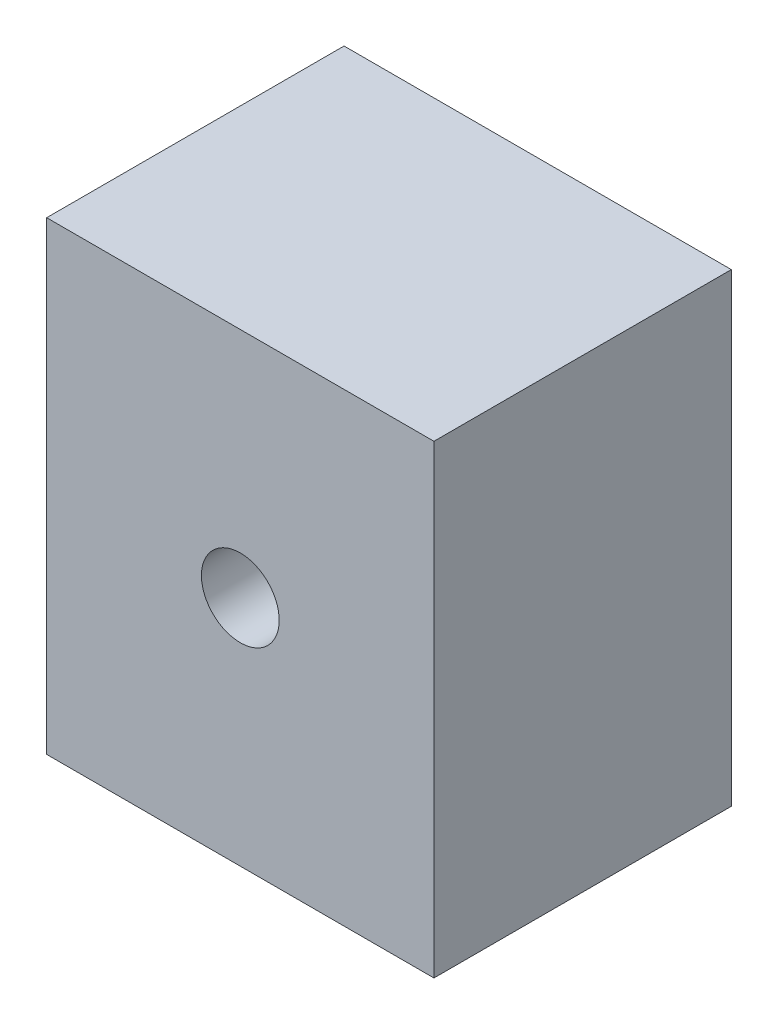
SolidWorks part; units mm, degrees
ref_plane "Front Plane" through (0, 0, 0) normal (0, 0, 1) x (1, 0, 0)
ref_plane "Top Plane" through (0, 0, 0) normal (0, 1, 0) x (1, 0, 0)
ref_plane "Right Plane" through (0, 0, 0) normal (1, 0, 0) x (0, 0, -1)
sketch "Sketch1" plane through (0, 0, 0) normal (0, 1, 0) x (1, 0, 0)
  line L1 (-8.4644, 10) -> (8.4644, 10)
  line L2 (-8.4644, 10) -> (-8.4644, -3)
  line L3 (-8.4644, -3) -> (8.4644, -3)
  line L4 (8.4644, 10) -> (8.4644, -3)
extrude "Boss-Extrude1" add sketch "Sketch1" along normal mid plane 20.32 separate body
sketch "Sketch2" plane through (0, 0, -10) normal (0, 0, -1) x (-1, 0, 0)
  line L1 (2.8001, 0) -> (1.4001, 2.425)
  line L2 (1.4001, 2.425) -> (-1.4001, 2.425)
  line L3 (-1.4001, 2.425) -> (-2.8001, 0)
  line L4 (-2.8001, 0) -> (-1.4001, -2.425)
  line L5 (-1.4001, -2.425) -> (1.4001, -2.425)
  line L6 (1.4001, -2.425) -> (2.8001, 0)
  circle A0 centre (0, 0) radius 2.425 construction
  circle A1 centre (0, 0) radius 1.7
extrude "Cut-Extrude1" cut sketch "Sketch2" against normal blind 9.906 contours L5 L6 L1 L2 L3 L4 A1 region at (-2.036, -1.1755, -10)
extrude "Cut-Extrude2" cut sketch "Sketch2<3>" against normal blind 15.748 contours A1 region at (0, 0, -10)
sketch "Sketch2<3>" plane through (0, 0, -10) normal (0, 0, -1) x (-1, 0, 0) same geometry as "Sketch2"
